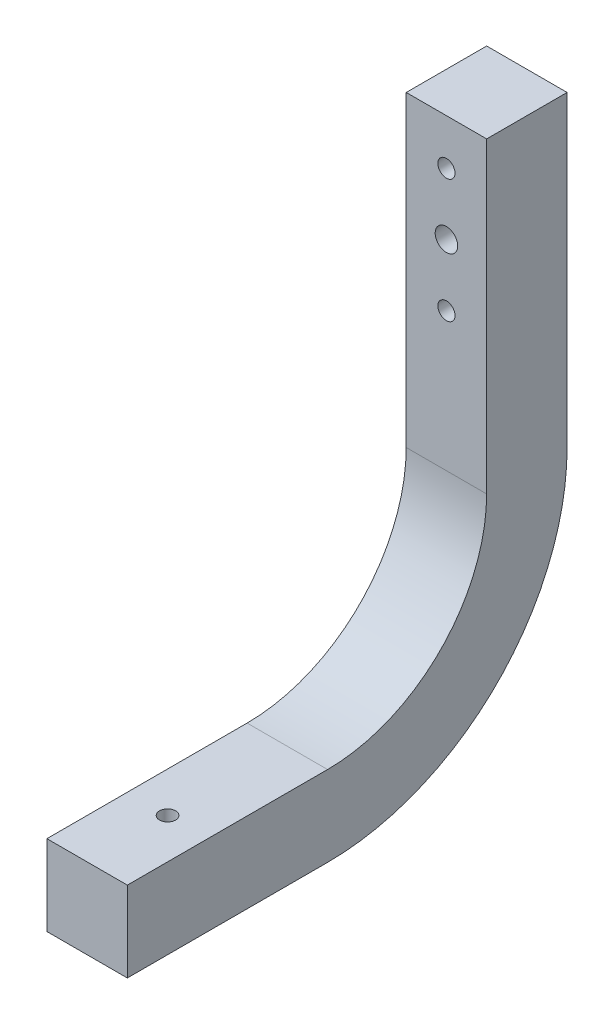
SolidWorks part; units mm, degrees
ref_plane "Front Plane" through (0, 0, 0) normal (0, 0, 1) x (1, 0, 0)
ref_plane "Top Plane" through (0, 0, 0) normal (0, 1, 0) x (1, 0, 0)
ref_plane "Right Plane" through (0, 0, 0) normal (1, 0, 0) x (0, 0, -1)
ref_axis "Z" through (0, 0, 86.1) along (0, 0, -1)
sketch "Sketch1" plane through (0, 0, 0) normal (1, 0, 0) x (0, 0, -1)
  line L0 (-15, 20) -> (0, 20)
  line L1 (0, 20) -> (0, -37.3333)
  line L2 (0, -32) -> (-50, -82) construction
  line L3 (-44.6667, -82) -> (-67, -82)
  line L4 (-67, -82) -> (-67, -67) construction
  line L5 (-67, -67) -> (-44.6667, -67)
  line L6 (-56.2132, -67) -> (-15, -25.7868) construction
  line L7 (-15, -37.3333) -> (-15, 20)
  line L8 (-35.6066, -46.3934) -> (-25, -57) construction
  line L9 (-44.6667, -67) -> (-56.2132, -67) construction
  line L10 (-67, -67) -> (-82, -67)
  line L11 (-67, -67) -> (-67, -82) construction
  line L12 (-67, -82) -> (-82, -82)
  line L13 (-82, -67) -> (-82, -82)
  line L14 (-15, -25.7868) -> (-15, -37.3333) construction
  line L15 (0, -37.3333) -> (0, -32) construction
  line L16 (-50, -82) -> (-44.6667, -82) construction
  arc A0 (-44.6667, -67) -> (-15, -37.3333) centre (-44.6667, -37.3333) ccw
  arc A1 (-44.6667, -82) -> (0, -37.3333) centre (-44.6667, -37.3333) ccw
  dimension "D1" = 15
  dimension "D2" = 67
  dimension "D3" = 82
  dimension "D4" = 20
  dimension "D5" = 135
  dimension "D6" = 50
  dimension "D7" = 15
  dimension "D8" = 22.3333
extrude "Boss-Extrude1" add sketch "Sketch1" along normal blind 7.5 and the other way blind 7.5
sketch "Sketch3" plane through (0, -67, 0) normal (0, 1, 0) x (1, 0, 0)
  line L0 (-8.25, 0) -> (8.25, 0) construction
  line L1 (0, -45.1) -> (0, 45.1) construction
  circle A0 centre (0, -67) radius 1.5
  dimension "D2" = 3
  dimension "D1" = 67
extrude "Cut-Extrude1" cut sketch "Sketch3" against normal through all
sketch "Sketch4" plane through (0, 0, 15) normal (0, 0, 1) x (1, 0, 0)
  line L0 (0, -11.5) -> (0, 11.5) construction
  circle A0 centre (0, 0) radius 2.1
  circle A1 centre (0, 11.5) radius 1.6
  circle A2 centre (0, -11.5) radius 1.6
  dimension "D1" = 4.2
  dimension "D3" = 3.2
  dimension "D2" = 23
extrude "Cut-Extrude2" cut sketch "Sketch4" against normal through all both and the other way through all
ref_axis "Axis1" through (0, -67, 67) along (0, 1, 0)
sketch "Sketch5" plane through (0, -82, 0) normal (0, -1, 0) x (1, 0, 0)
  circle A0 centre (0, 67) radius 2.275
  dimension "D1" = 4.55
extrude "Cut-Extrude3" cut sketch "Sketch5" against normal blind 6
sketch "Sketch6" plane through (0, -82, 0) normal (0, -1, 0) x (1, 0, 0)
  circle A0 centre (0, 67) radius 3.825
  dimension "D1" = 7.65
extrude "Cut-Extrude4" cut sketch "Sketch6" against normal blind 0.75
equation "\"rbracket-width\"= \"L2Thickness\""
equation "\"D1@Boss-Extrude1\"=\"rbracket-width\"/2"
equation "\"D2@Boss-Extrude1\"=\"rbracket-width\"/2"
equation "\"EyeCaptureRadius\"= ( \"EyeDiameter\" + \"EyeClearance\" ) / 2"
equation "\"rbracket_planetocenterline_dist\"= \"BasePlaneDistance\""
equation "\"D2@Sketch1\"=\"rbracket_planetocenterline_dist\""
equation "\"EyeDiameter\" = 100"
equation "\"BasePlaneDistance\" = \"EyeDiameter\"/2+\"L2Thickness\"+\"EyeClearance\""
equation "\"EyeClearance\" = 2"
equation "\"D1@Sketch1\"=\"rbracket-width\""
equation "\"D3@Sketch1\"=(\"EyeDiameter\"+\"EyeClearance\"+\"EyeClearance\")/2 + \"L2Thickness\" + \"rbracket-width\""
equation "\"D6@Sketch1\"=\"EyeDiameter\"/2"
equation "\"D7@Sketch1\"=\"rbracket-width\""
equation "\"D1@Sketch3\"=\"BasePlaneDistance\""
equation "\"L2Thickness\" = 15"
equation "\"D8@Sketch1\"=\"rbracket_planetocenterline_dist\"/3"
equation "\"BearingFlangeOD\"= 7.5"
equation "\"BearingFlangeThickness\"= 0.75"
equation "\"BearingHousingID\"=4.5"
equation "\"BearingDepth\"= 6"
equation "\"D1@Sketch5\"=\"BearingHousingID\" + \"PrinterFilamentThickness\" * \"ApplyPrinterOffsets\" / 2"
equation "\"D1@Cut-Extrude3\"=\"BearingDepth\""
equation "\"D1@Sketch6\"=\"BearingFlangeOD\" + \"PrinterFilamentThickness\" * 1.5 * \"ApplyPrinterOffsets\""
equation "\"D1@Cut-Extrude4\"=\"BearingFlangeThickness\""
equation "\"PrinterFilamentThickness\"= 0.1"
equation "\"ApplyPrinterOffsets\"= 1"
